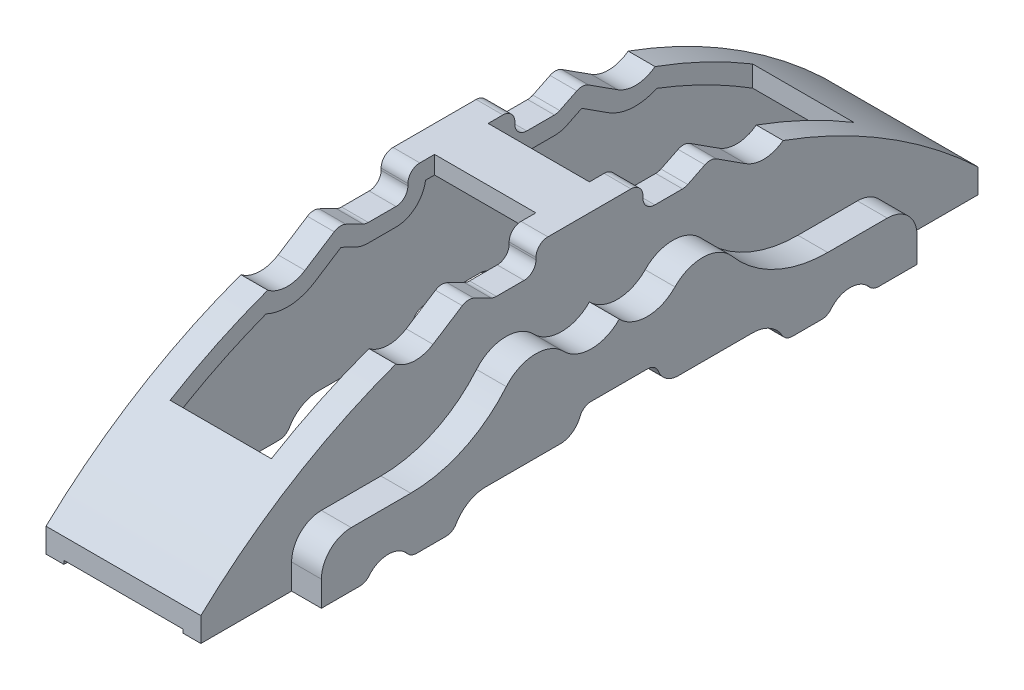
SolidWorks part; units mm, degrees
ref_plane "Front Plane" through (0, 0, 0) normal (0, 0, 1) x (1, 0, 0)
ref_plane "Top Plane" through (0, 0, 0) normal (0, 1, 0) x (1, 0, 0)
ref_plane "Right Plane" through (0, 0, 0) normal (1, 0, 0) x (0, 0, -1)
sketch "Sketch1" plane through (0, 0, 0) normal (1, 0, 0) x (0, 0, -1)
  line L0 (-57.9166, 0) -> (64.5121, 0) construction
  line L1 (0, 0) -> (0, 126.7569) construction
  line L2 (-65.2327, 65) -> (65.2327, 65) construction
  line L3 (4.7248, 72.4345) -> (-4.7248, 72.4345)
  line L4 (-9.9333, 68.8552) -> (-22.4047, 68.8552)
  line L5 (-29.0938, 65) -> (-34.0071, 65)
  line L6 (-43.5394, 65) -> (-58.2327, 65)
  line L7 (-65.2327, 65) -> (-65.2327, 69.0629)
  line L8 (65.2327, 65) -> (65.2327, 69.0629)
  line L9 (43.5394, 65) -> (58.2327, 65)
  line L10 (29.0938, 65) -> (34.0071, 65)
  line L11 (9.9333, 68.8552) -> (22.4047, 68.8552)
  line L12 (-65.2327, 65) -> (-58.2327, 65)
  line L13 (58.2327, 65) -> (65.2327, 65)
  line L14 (6.9761, 95) -> (-6.9761, 95)
  line L15 (-8.9761, 93) -> (-8.9761, 92.6681)
  line L16 (-10.9761, 90.6681) -> (-15.6252, 90.6681)
  line L17 (-16.5068, 90.8728) -> (-19.3856, 92.2866)
  line L18 (-21.3483, 92.174) -> (-26.2606, 89.0177)
  line L19 (21.3483, 92.174) -> (26.2606, 89.0177)
  line L20 (16.5068, 90.8728) -> (19.3856, 92.2866)
  line L21 (10.9761, 90.6681) -> (15.6252, 90.6681)
  line L22 (8.9761, 93) -> (8.9761, 92.6681)
  arc A0 (65.2327, 69.0629) -> (32.5084, 89.2648) centre (0, 0) ccw
  arc A1 (58.2327, 65) -> (-58.2327, 65) centre (0, 0) ccw
  arc A2 (-6.5919, 71.1514) -> (-9.9333, 68.8552) centre (-9.9333, 72.4345) cw
  arc A3 (-22.4047, 68.8552) -> (-27.3633, 65.9974) centre (-22.4047, 63.1245) ccw
  arc A4 (-35.5511, 65.7287) -> (-41.9954, 65.7287) centre (-38.7732, 63.0756) ccw
  arc A5 (-41.9954, 65.7287) -> (-43.5394, 65) centre (-43.5394, 67) cw
  arc A6 (-4.7248, 72.4345) -> (-6.5919, 71.1514) centre (-4.7248, 70.4345) ccw
  arc A7 (-27.3633, 65.9974) -> (-29.0938, 65) centre (-29.0938, 67) cw
  arc A8 (-34.0071, 65) -> (-35.5511, 65.7287) centre (-34.0071, 67) cw
  arc A9 (34.0071, 65) -> (35.5511, 65.7287) centre (34.0071, 67) ccw
  arc A10 (27.3633, 65.9974) -> (29.0938, 65) centre (29.0938, 67) ccw
  arc A11 (4.7248, 72.4345) -> (6.5919, 71.1514) centre (4.7248, 70.4345) cw
  arc A12 (41.9954, 65.7287) -> (43.5394, 65) centre (43.5394, 67) ccw
  arc A13 (35.5511, 65.7287) -> (41.9954, 65.7287) centre (38.7732, 63.0756) cw
  arc A14 (22.4047, 68.8552) -> (27.3633, 65.9974) centre (22.4047, 63.1245) cw
  arc A15 (6.5919, 71.1514) -> (9.9333, 68.8552) centre (9.9333, 72.4345) ccw
  arc A16 (-26.2606, 89.0177) -> (-32.5084, 89.2648) centre (-29.208, 93.6049) cw
  arc A17 (-19.3856, 92.2866) -> (-21.3483, 92.174) centre (-20.2672, 90.4914) ccw
  arc A18 (-15.6252, 90.6681) -> (-16.5068, 90.8728) centre (-15.6252, 92.6681) cw
  arc A19 (-6.9761, 95) -> (-8.9761, 93) centre (-6.9761, 93) ccw
  arc A20 (-8.9761, 92.6681) -> (-10.9761, 90.6681) centre (-10.9761, 92.6681) cw
  arc A21 (26.2606, 89.0177) -> (32.5084, 89.2648) centre (29.208, 93.6049) ccw
  arc A22 (8.9761, 92.6681) -> (10.9761, 90.6681) centre (10.9761, 92.6681) ccw
  arc A23 (6.9761, 95) -> (8.9761, 93) centre (6.9761, 93) cw
  arc A24 (15.6252, 90.6681) -> (16.5068, 90.8728) centre (15.6252, 92.6681) ccw
  arc A25 (19.3856, 92.2866) -> (21.3483, 92.174) centre (20.2672, 90.4914) cw
  arc A26 (-32.5084, 89.2648) -> (-65.2327, 69.0629) centre (0, 0) ccw
  point P6 (35.0695, 65)
  point P21 (-42.477, 65)
  point P26 (-27.8198, 65)
  point P29 (-35.0695, 65)
  point P51 (0, 72.4345)
  point P52 (27.8198, 65)
  point P53 (42.477, 65)
  point P62 (-20.3987, 92.7841)
  point P76 (0, 95)
  point P90 (20.3987, 92.7841)
  dimension "D1" = 174.54
  dimension "D2" = 190
  dimension "D4" = 2
  dimension "D6" = 2
  dimension "D3" = 65
  dimension "D5" = 7
extrude "Boss-Extrude1" add sketch "Sketch1" along normal blind 26 contours A11 A15 L11 A14 A10 L10 A9 A13 A12 L9 A1 L6 A5 A4 A8 L5 A7 A3 L4 A2 A6 L3 | A16 A26 L7 L12 A1 L13 L8 A0 A21 L19 A25 L20 A24 L21 A22 L22 A23 L14 A19 L15 A20 L16 A18 L17 A17 L18 region at (0, 75.2314, 0) region at (0, 88.6087, 0)
shell "Shell1" thickness 3 removed face at (13, 65, 54.3861) removed face at (13, 65.2778, 42.7265) removed face at (13, 65.2778, 34.8199) removed face at (13, 66.4891, 38.7732) removed face at (13, 65, 31.5505) removed face at (13, 67.7579, 25.0751) removed face at (13, 65.3829, 28.1618) removed face at (13, 68.8552, 16.169) removed face at (13, 65, -54.3861) removed face at (13, 65.2778, -42.7265) removed face at (13, 66.4891, -38.7732) removed face at (13, 65.2778, -34.8199) removed face at (13, 65.3829, -28.1618) removed face at (13, 65, -31.5505) removed face at (13, 67.7579, -25.0751) removed face at (13, 68.8552, -16.169) removed face at (13, 69.7439, -8.0844) removed face at (13, 71.9378, -5.758) removed face at (13, 71.9378, 5.758) removed face at (13, 69.7439, 8.0844) removed face at (13, 72.4345, 0)
fillet "Fillet1" radius 8 2 edges at (13, 65, 62.2327) (13, 65, -62.2327)
sketch "Sketch2" plane through (0, 0, 0) normal (0, 1, 0) x (1, 0, 0)
  line L0 (26, 32.5084) -> (26, 65.2327) construction
  line L1 (4.5, 48.9) -> (21.5, 48.9)
  line L2 (4.5, 48.9) -> (4.5, 4.5)
  line L3 (4.5, 4.5) -> (21.5, 4.5)
  line L4 (21.5, 48.9) -> (21.5, 4.5)
  line L5 (-14.3, 0) -> (14.3, 0) construction
  line L6 (4.5, -48.9) -> (21.5, -48.9)
  line L7 (21.5, -48.9) -> (21.5, -4.5)
  line L8 (4.5, -48.9) -> (4.5, -4.5)
  line L9 (4.5, -4.5) -> (21.5, -4.5)
  dimension "D1" = 4.5
  dimension "D2" = 4.5
  dimension "D3" = 44.4
  dimension "D4" = 4.5
extrude "Cut-Extrude2" cut sketch "Sketch2" against normal through all both and the other way through all
sketch "Sketch3" plane through (26, 0, 0) normal (1, 0, 0) x (0, 0, -1)
  line L0 (0, 95) -> (0, 72.4345) construction
  line L1 (6.9761, 95) -> (-6.9761, 95) construction
  line L2 (4.7248, 72.4345) -> (-4.7248, 72.4345) construction
  line L3 (-50, 65) -> (-50, 69.2397)
  line L4 (-43.5394, 65) -> (-65.2327, 65) construction
  line L5 (-45, 74.2397) -> (-35, 74.2397)
  line L6 (50, 65) -> (50, 69.2397)
  line L7 (45, 74.2397) -> (35, 74.2397)
  line L26 (9.9333, 68.8552) -> (22.4047, 68.8552)
  line L27 (29.0938, 65) -> (34.0071, 65)
  line L28 (43.5394, 65) -> (65.2327, 65)
  line L29 (65.2327, 65) -> (65.2327, 69.0629)
  line L30 (26.2606, 89.0177) -> (21.3483, 92.174)
  line L31 (19.3856, 92.2866) -> (16.5068, 90.8728)
  line L32 (15.6252, 90.6681) -> (10.9761, 90.6681)
  line L33 (8.9761, 92.6681) -> (8.9761, 93)
  line L34 (6.9761, 95) -> (-6.9761, 95)
  line L35 (-8.9761, 93) -> (-8.9761, 92.6681)
  line L36 (-10.9761, 90.6681) -> (-15.6252, 90.6681)
  line L37 (-16.5068, 90.8728) -> (-19.3856, 92.2866)
  line L38 (-21.3483, 92.174) -> (-26.2606, 89.0177)
  line L39 (-65.2327, 69.0629) -> (-65.2327, 65)
  line L40 (-65.2327, 65) -> (-43.5394, 65)
  line L41 (-34.0071, 65) -> (-29.0938, 65)
  line L42 (-22.4047, 68.8552) -> (-9.9333, 68.8552)
  line L43 (-4.7248, 72.4345) -> (4.7248, 72.4345)
  line L44 (9.9333, 68.8552) -> (22.4047, 68.8552)
  line L45 (29.0938, 65) -> (34.0071, 65)
  line L46 (43.5394, 65) -> (50, 65)
  line L58 (-50, 65) -> (-43.5394, 65)
  line L59 (-34.0071, 65) -> (-29.0938, 65)
  line L60 (-22.4047, 68.8552) -> (-9.9333, 68.8552)
  line L61 (-4.7248, 72.4345) -> (4.7248, 72.4345)
  arc A0 (-35, 74.2397) -> (-18.9535, 81.7103) centre (-35, 95.2087) ccw
  arc A1 (-18.9535, 81.7103) -> (-9.3594, 82.0488) centre (-14.0036, 77.5464) cw
  arc A2 (-9.3594, 82.0488) -> (0, 82.0488) centre (-4.6797, 86.5857) ccw
  arc A3 (35, 74.2397) -> (18.9535, 81.7103) centre (35, 95.2087) cw
  arc A4 (9.3594, 82.0488) -> (0, 82.0488) centre (4.6797, 86.5857) cw
  arc A5 (18.9535, 81.7103) -> (9.3594, 82.0488) centre (14.0036, 77.5464) ccw
  arc A6 (50, 69.2397) -> (45, 74.2397) centre (45, 69.2397) ccw
  arc A7 (-50, 69.2397) -> (-45, 74.2397) centre (-45, 69.2397) cw
  arc A34 (6.5919, 71.1514) -> (4.7248, 72.4345) centre (4.7248, 70.4345) ccw
  arc A35 (6.5919, 71.1514) -> (9.9333, 68.8552) centre (9.9333, 72.4345) ccw
  arc A36 (27.3633, 65.9974) -> (22.4047, 68.8552) centre (22.4047, 63.1245) ccw
  arc A37 (27.3633, 65.9974) -> (29.0938, 65) centre (29.0938, 67) ccw
  arc A38 (34.0071, 65) -> (35.5511, 65.7287) centre (34.0071, 67) ccw
  arc A39 (41.9954, 65.7287) -> (35.5511, 65.7287) centre (38.7732, 63.0756) ccw
  arc A40 (41.9954, 65.7287) -> (43.5394, 65) centre (43.5394, 67) ccw
  arc A41 (65.2327, 69.0629) -> (32.5084, 89.2648) centre (0, 0) ccw
  arc A42 (26.2606, 89.0177) -> (32.5084, 89.2648) centre (29.208, 93.6049) ccw
  arc A43 (21.3483, 92.174) -> (19.3856, 92.2866) centre (20.2672, 90.4914) ccw
  arc A44 (15.6252, 90.6681) -> (16.5068, 90.8728) centre (15.6252, 92.6681) ccw
  arc A45 (8.9761, 92.6681) -> (10.9761, 90.6681) centre (10.9761, 92.6681) ccw
  arc A46 (8.9761, 93) -> (6.9761, 95) centre (6.9761, 93) ccw
  arc A47 (-6.9761, 95) -> (-8.9761, 93) centre (-6.9761, 93) ccw
  arc A48 (-10.9761, 90.6681) -> (-8.9761, 92.6681) centre (-10.9761, 92.6681) ccw
  arc A49 (-16.5068, 90.8728) -> (-15.6252, 90.6681) centre (-15.6252, 92.6681) ccw
  arc A50 (-19.3856, 92.2866) -> (-21.3483, 92.174) centre (-20.2672, 90.4914) ccw
  arc A51 (-32.5084, 89.2648) -> (-26.2606, 89.0177) centre (-29.208, 93.6049) ccw
  arc A52 (-32.5084, 89.2648) -> (-65.2327, 69.0629) centre (0, 0) ccw
  arc A53 (-43.5394, 65) -> (-41.9954, 65.7287) centre (-43.5394, 67) ccw
  arc A54 (-35.5511, 65.7287) -> (-41.9954, 65.7287) centre (-38.7732, 63.0756) ccw
  arc A55 (-35.5511, 65.7287) -> (-34.0071, 65) centre (-34.0071, 67) ccw
  arc A56 (-29.0938, 65) -> (-27.3633, 65.9974) centre (-29.0938, 67) ccw
  arc A57 (-22.4047, 68.8552) -> (-27.3633, 65.9974) centre (-22.4047, 63.1245) ccw
  arc A58 (-9.9333, 68.8552) -> (-6.5919, 71.1514) centre (-9.9333, 72.4345) ccw
  arc A59 (-4.7248, 72.4345) -> (-6.5919, 71.1514) centre (-4.7248, 70.4345) ccw
  arc A60 (6.5919, 71.1514) -> (4.7248, 72.4345) centre (4.7248, 70.4345) ccw
  arc A61 (6.5919, 71.1514) -> (9.9333, 68.8552) centre (9.9333, 72.4345) ccw
  arc A62 (27.3633, 65.9974) -> (22.4047, 68.8552) centre (22.4047, 63.1245) ccw
  arc A63 (27.3633, 65.9974) -> (29.0938, 65) centre (29.0938, 67) ccw
  arc A64 (34.0071, 65) -> (35.5511, 65.7287) centre (34.0071, 67) ccw
  arc A65 (41.9954, 65.7287) -> (35.5511, 65.7287) centre (38.7732, 63.0756) ccw
  arc A66 (41.9954, 65.7287) -> (43.5394, 65) centre (43.5394, 67) ccw
  arc A79 (-43.5394, 65) -> (-41.9954, 65.7287) centre (-43.5394, 67) ccw
  arc A80 (-35.5511, 65.7287) -> (-41.9954, 65.7287) centre (-38.7732, 63.0756) ccw
  arc A81 (-35.5511, 65.7287) -> (-34.0071, 65) centre (-34.0071, 67) ccw
  arc A82 (-29.0938, 65) -> (-27.3633, 65.9974) centre (-29.0938, 67) ccw
  arc A83 (-22.4047, 68.8552) -> (-27.3633, 65.9974) centre (-22.4047, 63.1245) ccw
  arc A84 (-9.9333, 68.8552) -> (-6.5919, 71.1514) centre (-9.9333, 72.4345) ccw
  arc A85 (-4.7248, 72.4345) -> (-6.5919, 71.1514) centre (-4.7248, 70.4345) ccw
  point P40 (50, 74.2397)
  point P43 (-50, 74.2397)
  dimension "D2" = 5
  dimension "D1" = 15
  dimension "D3" = 50
  dimension "D4" = 0
extrude "Boss-Extrude2" add sketch "Sketch3" along normal blind 5
scale "Scale1" scale about centroid uniform scaling yes scale factor 2
